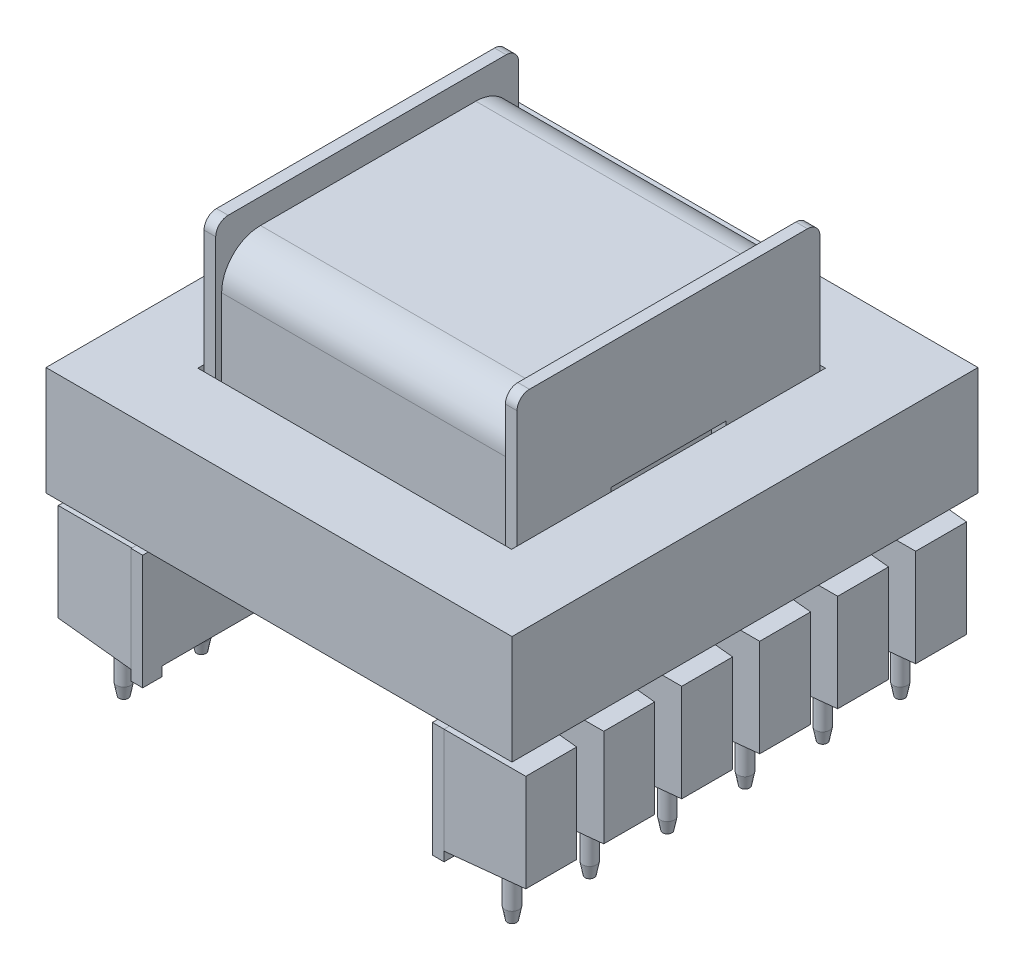
SolidWorks part; units mm, degrees
ref_plane "Front Plane" through (0, 0, 0) normal (0, 0, 1) x (1, 0, 0)
ref_plane "Top Plane" through (0, 0, 0) normal (0, 1, 0) x (1, 0, 0)
ref_plane "Right Plane" through (0, 0, 0) normal (1, 0, 0) x (0, 0, -1)
sketch "Sketch2" plane through (0, 0, 0) normal (0, 1, 0) x (1, 0, 0)
  line L0 (-23.9822, 0) -> (19.1858, 0) construction
  line L1 (-9.5141, 9.75) -> (-9.5141, -9.75)
  line L2 (-9.5141, -9.75) -> (-8.7641, -9.75)
  line L3 (-8.7641, -9.75) -> (-8.7641, -4.35)
  line L4 (-8.7641, -4.35) -> (9.8859, -4.35)
  line L5 (9.8859, -4.35) -> (9.8859, -9.75)
  line L6 (9.8859, -9.75) -> (10.6359, -9.75)
  line L7 (10.6359, -9.75) -> (10.6359, 9.75)
  line L8 (10.6359, 9.75) -> (9.8859, 9.75)
  line L9 (9.8859, 9.75) -> (9.8859, 4.35)
  line L10 (9.8859, 4.35) -> (-8.7641, 4.35)
  line L11 (-8.7641, 4.35) -> (-8.7641, 9.75)
  line L12 (-8.7641, 9.75) -> (-9.5141, 9.75)
  line L13 (-9.5141, 0) -> (0.5609, 0) construction
  line L14 (0.5609, 0) -> (10.6359, 0) construction
  line L15 (3.2449, 4.35) -> (3.2449, 0) construction
  line L16 (3.2449, 0) -> (3.2449, -4.35) construction
  dimension "D1" = 18.65
  dimension "D2" = 0.75
  dimension "D3" = 19.5
  dimension "D4" = 5.4
extrude "Boss-Extrude1" add sketch "Sketch2" along normal blind 11.8 and the other way blind 11.8
sketch "Sketch3" plane through (0, 0, 4.35) normal (0, 0, 1) x (1, 0, 0)
  line L0 (9.8859, -11.8) -> (9.8859, 11.8) construction
  line L1 (-8.7641, 11.8) -> (9.8859, 11.8)
  line L2 (-8.7641, 11.8) -> (-8.7641, 4.4)
  line L3 (-8.7641, 4.4) -> (9.8859, 4.4)
  line L4 (9.8859, 11.8) -> (9.8859, 4.4)
  line L5 (-8.7641, -11.8) -> (-8.7641, 11.8) construction
  line L6 (9.8859, -11.8) -> (-8.7641, -11.8)
  line L7 (9.8859, -11.8) -> (9.8859, -4.4)
  line L8 (9.8859, -4.4) -> (-8.7641, -4.4)
  line L9 (-8.7641, -11.8) -> (-8.7641, -4.4)
  dimension "D1" = 8.8
extrude "Cut-Extrude1" cut sketch "Sketch3" against normal blind 11.8
sketch "Sketch4" plane through (10.6359, 0, 0) normal (1, 0, 0) x (0, 0, -1)
  line L0 (-3.7, 0) -> (-9.75, 0) construction
  line L1 (-3.7, -3.7) -> (3.7, -3.7)
  line L2 (-3.7, -3.7) -> (-3.7, 3.7)
  line L3 (-3.7, 3.7) -> (3.7, 3.7)
  line L4 (3.7, -3.7) -> (3.7, 3.7)
  line L5 (-9.75, -11.8) -> (-9.75, 11.8) construction
  line L6 (3.7, 0) -> (9.75, 0) construction
  line L7 (9.75, -11.8) -> (9.75, 11.8) construction
  line L8 (0.9687, 3.7) -> (0.9687, 11.8) construction
  line L10 (0.9687, -3.7) -> (0.9687, -11.8) construction
  line L11 (-9.75, -11.8) -> (9.75, -11.8) construction
  line L12 (-9.75, 11.8) -> (9.75, 11.8) construction
  dimension "D1" = 7.4
extrude "Cut-Extrude2" cut sketch "Sketch4" against normal blind 25
fillet "Fillet1" radius 0.8 8 edges at (0.5609, 4.4, -4.35) (0.5609, -4.4, -4.35) (0.5609, 4.4, 4.35) (0.5609, -4.4, 4.35) (-9.1391, 11.8, -9.75) (10.2609, 11.8, -9.75) (-9.1391, 11.8, 9.75) (10.2609, 11.8, 9.75)
sketch "Sketch5" plane through (0, 0, 9.75) normal (0, 0, 1) x (1, 0, 0)
  line L0 (-9.5141, -11.8) -> (-9.5141, 11) construction
  line L1 (9.8859, -4.4) -> (10.6359, -4.4)
  line L2 (9.8859, -4.4) -> (9.8859, -11.8)
  line L3 (9.8859, -11.8) -> (10.6359, -11.8)
  line L4 (10.6359, -4.4) -> (10.6359, -11.8)
  line L5 (-8.7641, -11.8) -> (-9.5141, -11.8)
  line L6 (-8.7641, -11.8) -> (-8.7641, -4.4)
  line L7 (-8.7641, -4.4) -> (-9.5141, -4.4)
  line L8 (-9.5141, -11.8) -> (-9.5141, -4.4)
extrude "Boss-Extrude2" add sketch "Sketch5" along normal blind 4.7 and the other way blind 24.2
sketch "Sketch6" plane through (-9.5141, 0, 0) normal (-1, 0, 0) x (0, 0, 1)
  line L0 (-14.45, -11.8) -> (14.45, -11.8) construction
  line L1 (-13.2, -11.8) -> (13.2, -11.8)
  line L2 (-13.2, -11.8) -> (-13.2, -11.2)
  line L3 (-13.2, -11.2) -> (13.2, -11.2)
  line L4 (13.2, -11.8) -> (13.2, -11.2)
  line L5 (-14.45, -4.4) -> (-14.45, -11.8) construction
  line L6 (14.45, -4.4) -> (14.45, -11.8) construction
  dimension "D1" = 1.25
  dimension "D2" = 1.25
  dimension "D3" = 0.6
extrude "Cut-Extrude3" cut sketch "Sketch6" against normal blind 25.3
sketch "Sketch7" plane through (-9.5141, 0, 0) normal (-1, 0, 0) x (0, 0, 1)
  line L0 (13.2, -11.2) -> (-13.2, -11.2) construction
  line L1 (-10.6, -4.4) -> (-14.4, -4.4)
  line L2 (-14.4, -4.4) -> (-14.4, -11.2)
  line L3 (-14.4, -11.2) -> (-10.6, -11.2)
  line L4 (-10.6, -4.4) -> (-10.6, -11.2)
  line L5 (-14.45, -4.4) -> (-9.75, -4.4) construction
  line L6 (-9.4, -4.4) -> (-5.6, -4.4)
  line L7 (-9.4, -4.4) -> (-9.4, -11.2)
  line L8 (-9.4, -11.2) -> (-5.6, -11.2)
  line L9 (-5.6, -4.4) -> (-5.6, -11.2)
  line L10 (-10.6, -7.0073) -> (-9.4, -7.0073) construction
  line L11 (-4.4, -4.4) -> (-0.6, -4.4)
  line L12 (-4.4, -4.4) -> (-4.4, -11.2)
  line L13 (-4.4, -11.2) -> (-0.6, -11.2)
  line L14 (-0.6, -4.4) -> (-0.6, -11.2)
  line L15 (0.6, -4.4) -> (4.4, -4.4)
  line L16 (0.6, -4.4) -> (0.6, -11.2)
  line L17 (0.6, -11.2) -> (4.4, -11.2)
  line L18 (4.4, -4.4) -> (4.4, -11.2)
  line L19 (5.6, -4.4) -> (9.4, -4.4)
  line L20 (5.6, -4.4) -> (5.6, -11.2)
  line L21 (5.6, -11.2) -> (9.4, -11.2)
  line L22 (9.4, -4.4) -> (9.4, -11.2)
  line L23 (10.6, -4.4) -> (14.4, -4.4)
  line L24 (9.75, -4.4) -> (14.45, -4.4) construction
  line L25 (14.4, -4.4) -> (14.4, -11.2)
  line L26 (10.6, -4.4) -> (10.6, -11.2)
  line L27 (-5.6, -7.0073) -> (-4.4, -7.0073) construction
  line L28 (-0.6, -7.0073) -> (0.6, -7.0073) construction
  line L29 (4.4, -7.0073) -> (5.6, -7.0073) construction
  line L30 (9.4, -7.0073) -> (10.6, -7.0073) construction
  line L31 (14.4, -11.2) -> (10.6, -11.2)
  dimension "D1" = 3.8
  dimension "D2" = 1.2
  dimension "D3" = 0.6
extrude "Boss-Extrude3" add sketch "Sketch7" along normal blind 5 draft 3
sketch "Sketch8" plane through (10.6359, 0, -10.6359) normal (-1, 0, 0) x (0, 0, 1)
  line L1 (-3.8141, -4.4) -> (-0.0141, -4.4)
  line L2 (-3.8141, -4.4) -> (-3.8141, -11.2)
  line L3 (-3.8141, -11.2) -> (-0.0141, -11.2)
  line L4 (-0.0141, -4.4) -> (-0.0141, -11.2)
  line L6 (1.2059, -4.4) -> (5.0059, -4.4)
  line L7 (1.2059, -4.4) -> (1.2059, -11.2)
  line L8 (1.2059, -11.2) -> (5.0059, -11.2)
  line L9 (5.0059, -4.4) -> (5.0059, -11.2)
  line L10 (-0.0141, -7.0073) -> (1.2059, -7.0073) construction
  line L11 (6.2259, -4.4) -> (10.0259, -4.4)
  line L12 (6.2259, -4.4) -> (6.2259, -11.2)
  line L13 (6.2259, -11.2) -> (10.0259, -11.2)
  line L14 (10.0259, -4.4) -> (10.0259, -11.2)
  line L15 (11.2459, -4.4) -> (15.0459, -4.4)
  line L16 (11.2459, -4.4) -> (11.2459, -11.2)
  line L17 (11.2459, -11.2) -> (15.0459, -11.2)
  line L18 (15.0459, -4.4) -> (15.0459, -11.2)
  line L19 (16.2659, -4.4) -> (20.0659, -4.4)
  line L20 (16.2659, -4.4) -> (16.2659, -11.2)
  line L21 (16.2659, -11.2) -> (20.0659, -11.2)
  line L22 (20.0659, -4.4) -> (20.0659, -11.2)
  line L23 (25.0859, -4.4) -> (21.2859, -4.4)
  line L24 (25.0859, -4.4) -> (25.0859, -11.2)
  line L25 (25.0859, -11.2) -> (21.2859, -11.2)
  line L26 (21.2859, -4.4) -> (21.2859, -11.2)
  line L27 (5.0059, -7.0073) -> (6.2259, -7.0073) construction
  line L28 (10.0259, -7.0073) -> (11.2459, -7.0073) construction
  line L29 (15.0459, -7.0073) -> (16.2659, -7.0073) construction
  line L30 (20.0659, -7.0073) -> (21.2859, -7.0073) construction
  line L31 (25.0859, -11.8) -> (25.0859, -4.4) construction
  line L32 (20.3859, -4.4) -> (25.0859, -4.4) construction
  line L33 (-3.8141, -11.8) -> (-3.8141, -4.4) construction
  dimension "D1" = 3.8
extrude "Boss-Extrude4" add sketch "Sketch8" against normal blind 5 draft 3
ref_plane "Plane1" through (0, -14, 0) normal (0, 1, 0) x (1, 0, 0)
sketch "Sketch9" plane through (0, -14, 0) normal (0, 1, 0) x (1, 0, 0)
  line L0 (-11.9391, 18.9532) -> (-11.9391, -19.3621) construction
  line L1 (13.0609, 18.9532) -> (13.0609, -19.872) construction
  line L2 (-11.9391, -0.8986) -> (-8.7641, -0.8986) construction
  line L3 (-8.7641, 13.2) -> (-8.7641, -13.2) construction
  line L4 (13.0609, 0) -> (9.8859, 0) construction
  line L5 (9.8859, 3.55) -> (9.8859, -3.55) construction
  line L6 (-9.5141, -14.45) -> (-8.7641, -14.45) construction
  circle A0 centre (-11.9391, 12.5) radius 0.45
  circle A1 centre (-11.9391, 7.5) radius 0.45
  circle A2 centre (-11.9391, 2.5) radius 0.45
  circle A3 centre (-11.9391, -2.5) radius 0.45
  circle A4 centre (-11.9391, -7.5) radius 0.45
  circle A5 centre (-11.9391, -12.5) radius 0.45
  circle A6 centre (13.0609, -12.5) radius 0.45
  circle A7 centre (13.0609, -7.5) radius 0.45
  circle A8 centre (13.0609, -2.5) radius 0.45
  circle A9 centre (13.0609, 2.5) radius 0.45
  circle A10 centre (13.0609, 7.5) radius 0.45
  circle A11 centre (13.0609, 12.5) radius 0.45
  dimension "D1" = 25
  dimension "D2" = 5
  dimension "D3" = 5
  dimension "D4" = 1.95
  dimension "D5" = 5
  dimension "D6" = 5
  dimension "D7" = 5
extrude "Boss-Extrude5" add sketch "Sketch9" along normal blind 4 and the other way blind 0.8 draft 11
sketch "Sketch12" plane through (0, 0, 0) normal (0, 1, 0) x (1, 0, 0)
  line L0 (-14.4391, 0.501) -> (-9.5141, 0.501) construction
  line L1 (-14.4391, 15) -> (15.5609, 15)
  line L2 (-14.4391, 15) -> (-14.4391, -15)
  line L3 (-14.4391, -15) -> (15.5609, -15)
  line L4 (15.5609, 15) -> (15.5609, -15)
  line L6 (10.6359, 0) -> (15.5609, 0) construction
  line L7 (10.6359, -8.95) -> (10.6359, 8.95) construction
  line L8 (-8.7641, 4.35) -> (9.8859, 4.35) construction
  line L9 (-0.7352, 4.35) -> (-0.7352, 15) construction
  line L10 (-0.7352, -4.35) -> (-0.7352, -15) construction
  line L11 (9.8859, -4.35) -> (-8.7641, -4.35) construction
  line L12 (-14.5141, 5.862) -> (-14.5141, 9.138) construction
  line L13 (-9.5141, 10.05) -> (10.6859, 10.05)
  line L14 (-9.5141, 10.05) -> (-9.5141, -10.15)
  line L15 (-9.5141, -10.15) -> (10.6859, -10.15)
  line L16 (10.6859, 10.05) -> (10.6859, -10.15)
  dimension "D1" = 30
  dimension "D2" = 5.7
  dimension "D3" = 20.2
  dimension "D4" = 5
extrude "Boss-Extrude6" add sketch "Sketch12" along normal blind 3.5 and the other way blind 3.5
sketch "Sketch13" plane through (0, 0, 0) normal (1, 0, 0) x (0, 0, -1)
  line L0 (-9.43, -11.2) -> (-9.43, -4.4) construction
  line L1 (9.43, 10.2514) -> (-9.43, 10.2514)
  line L2 (9.43, 10.2514) -> (9.43, -10.2514)
  line L3 (9.43, -10.2514) -> (-9.43, -10.2514)
  line L4 (-9.43, 10.2514) -> (-9.43, -10.2514)
  line L5 (9.43, 10.2514) -> (-9.43, -10.2514) construction
  line L6 (9.43, -10.2514) -> (-9.43, 10.2514) construction
  point P0 (0, 0)
extrude "Boss-Extrude7" add sketch "Sketch13" along normal blind 9.7 and the other way blind 8.7
fillet "Fillet3" radius 2.5 4 edges at (0.5, -10.2514, -9.43) (0.5, -10.2514, 9.43) (0.5, 10.2514, -9.43) (0.5, 10.2514, 9.43)
